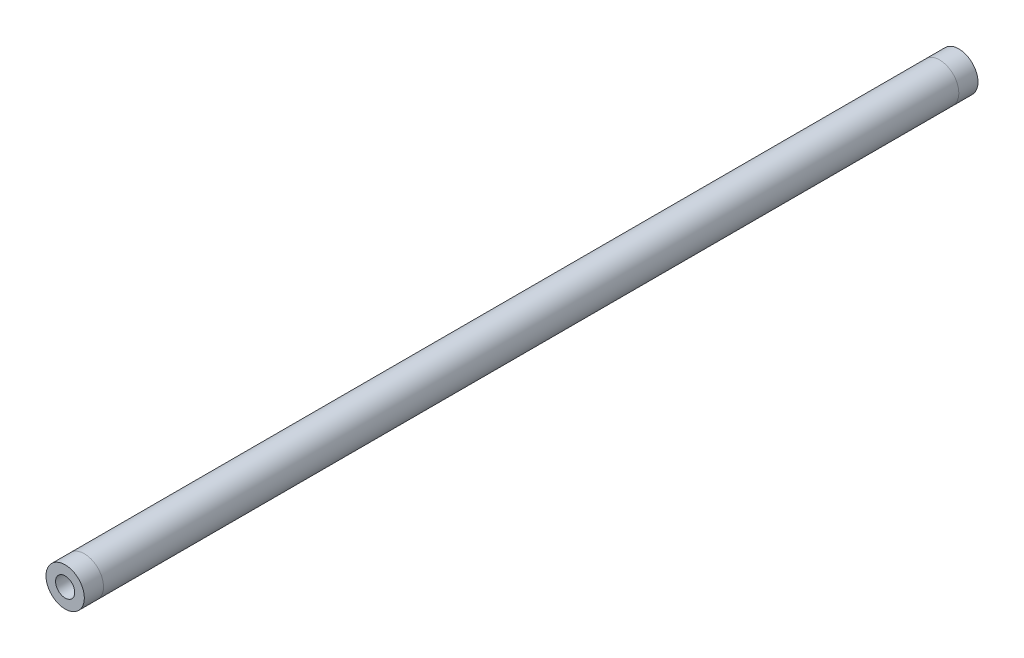
SolidWorks part; units mm, degrees
material "AISI 4130 Steel, normalized at 870C"
ref_plane "Front Plane" through (0, 0, 0) normal (0, 0, 1) x (1, 0, 0)
ref_plane "Top Plane" through (0, 0, 0) normal (0, 1, 0) x (1, 0, 0)
ref_plane "Right Plane" through (0, 0, 0) normal (1, 0, 0) x (0, 0, -1)
sketch "Axis" plane through (0, 0, 0) normal (0, 1, 0) x (1, 0, 0)
  line L0 (0, 0) -> (0, 21.9075) construction
  line L1 (0, 21.9075) -> (0, 317.7011) construction
  line L2 (0, 317.7011) -> (0, 339.6086) construction
  dimension "D1" = 21.9075
  dimension "D2" = 339.6086
sketch "Sketch2" plane through (0, 0, 0) normal (0, 0, 1) x (1, 0, 0)
  circle A0 centre (0, 0) radius 6.35
  circle A1 centre (0, 0) radius 3.175
  circle A2 centre (0, 0) radius 5.461
  dimension "D1" = 12.7
  dimension "D2" = 6.35
  dimension "D3" = 10.922
extrude "Threaded Insert 1-1" add sketch "Sketch2" against normal blind 6.35 from vertex contours A0 A2 | A2 A1 region at (-6.1704, 0, 0) region at (-5.3065, 0, 0) starting at point (0, 0, -21.9075)
extrude "Threaded Insert 1-2" add sketch "Sketch2<5>" against normal blind 6.35 from surface contours A2 A1 region at (-5.3065, 0, 0) starting at face at (6.35, 0, -28.2575)
sketch "Sketch2<5>" plane through (0, 0, 0) normal (0, 0, 1) x (1, 0, 0) same geometry as "Sketch2"
extrude "Boss-Extrude4" add sketch "Sketch2<7>" along normal blind 6.35 from vertex separate body contours A0 A2 | A2 A1 region at (-6.1704, 0, 0) region at (-5.3065, 0, 0) starting at point (0, 0, -317.7011)
sketch "Sketch2<7>" plane through (0, 0, 0) normal (0, 0, 1) x (1, 0, 0) same geometry as "Sketch2"
extrude "Boss-Extrude5" add sketch "Sketch2<8>" along normal blind 6.35 from surface contours A2 A1 region at (-5.3065, 0, 0) starting at face at (6.35, 0, -311.3511)
sketch "Sketch2<8>" plane through (0, 0, 0) normal (0, 0, 1) x (1, 0, 0) same geometry as "Sketch2"
extrude "Boss-Extrude6" add sketch "Sketch2<9>" against normal up to surface (311.3511 mm away) from surface separate body contours A0 A2 region at (-6.1704, 0, 0) up to face at (5.461, 0, -311.3511) starting at face at (5.461, 0, -28.2575)
sketch "Sketch2<9>" plane through (0, 0, 0) normal (0, 0, 1) x (1, 0, 0) same geometry as "Sketch2"
move or copy body "Body-Move/Copy1" [suppressed] bodies to move or copy 102 105 106 parameters "D1"=0, "D2"=0, "D3"=0
equation "\"Tube Outer Diameter\"= .5"
equation "\"Tube Inner Diameter\"= .430"
equation "\"Rod end Diameter\"= .25"
equation "\"Threaded Insert Out\"= .25"
equation "\"Threaded Insert In\"= .25'`"
equation "\"D1@Sketch2\"=\"Tube Outer Diameter\""
equation "\"D2@Sketch2\"=\"Rod end Diameter\""
equation "\"D1@Threaded Insert 1-1\" = \"Threaded Insert Out\""
equation "\"D3@Sketch2\"=\"Tube Inner Diameter\""
equation "\"D1@Threaded Insert 1-2\" = \"Threaded Insert In\""
equation "\"D1@Boss-Extrude4\"=\"Threaded Insert Out\""
equation "\"D1@Boss-Extrude5\"=\"Threaded Insert In\""
